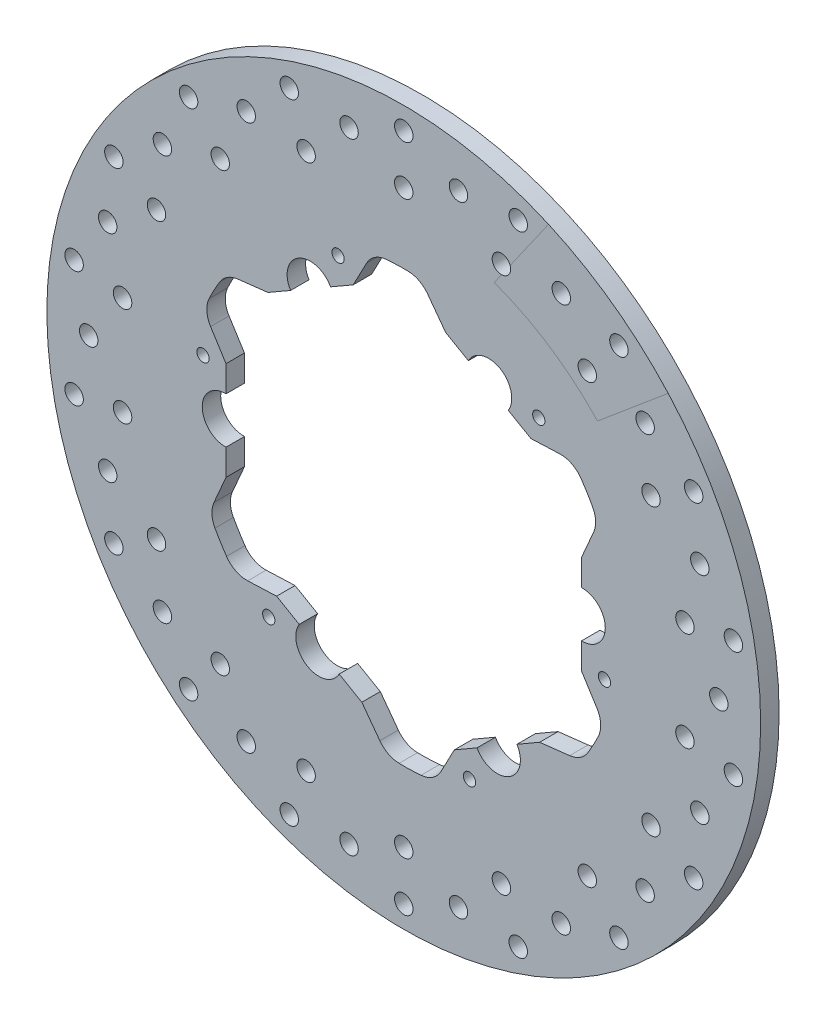
SolidWorks part; units mm, degrees
material "Gray Cast Iron"
ref_plane "Front Plane" through (0, 0, 0) normal (0, 0, 1) x (1, 0, 0)
ref_plane "Top Plane" through (0, 0, 0) normal (0, 1, 0) x (1, 0, 0)
ref_plane "Right Plane" through (0, 0, 0) normal (1, 0, 0) x (0, 0, -1)
sketch "Sketch1" plane through (0, 0, 0) normal (0, 0, 1) x (1, 0, 0)
  line L0 (-55.5625, 0) -> (-55.5625, -25.0191) construction
  line L1 (-45.8597, 11.4094) -> (-45.8597, 4.6599)
  line L2 (-45.8597, 11.4094) -> (-51.6236, 20.5474)
  line L3 (-45.8597, -13.9906) -> (-50.1583, -23.9026)
  line L4 (-45.8597, -7.2411) -> (-45.8597, -13.9906)
  line L5 (-13.049, 45.4204) -> (-8.0172, 54.981)
  line L6 (-13.049, 45.4204) -> (-18.8943, 42.0456)
  line L7 (-29.2008, 36.0951) -> (-35.0461, 32.7204)
  line L8 (-35.0461, 32.7204) -> (-45.7794, 31.4871)
  line L9 (32.8107, 34.011) -> (43.6064, 34.4336)
  line L10 (32.8107, 34.011) -> (26.9654, 37.3857)
  line L11 (16.6589, 43.3362) -> (10.8136, 46.711)
  line L12 (10.8136, 46.711) -> (4.3789, 55.3897)
  line L13 (45.8597, -11.4094) -> (51.6236, -20.5474)
  line L14 (45.8597, -11.4094) -> (45.8597, -4.6599)
  line L15 (45.8597, 7.2411) -> (45.8597, 13.9906)
  line L16 (45.8597, 13.9906) -> (50.1583, 23.9026)
  line L17 (13.049, -45.4204) -> (8.0172, -54.981)
  line L18 (13.049, -45.4204) -> (18.8943, -42.0456)
  line L19 (29.2008, -36.0951) -> (35.0461, -32.7204)
  line L20 (35.0461, -32.7204) -> (45.7794, -31.4871)
  line L21 (-32.8107, -34.011) -> (-43.6064, -34.4336)
  line L22 (-32.8107, -34.011) -> (-26.9654, -37.3857)
  line L23 (-16.6589, -43.3362) -> (-10.8136, -46.711)
  line L24 (-10.8136, -46.711) -> (-4.3789, -55.3897)
  circle A0 centre (0, 0) radius 92.075
  arc A1 (-45.7794, 31.4871) -> (-51.6236, 20.5474) centre (0, 0) ccw
  arc A3 (-45.8597, 4.6599) -> (-45.8597, -7.2411) centre (-46.0375, -1.2906) ccw
  arc A4 (-18.8943, 42.0456) -> (-29.2008, 36.0951) centre (-24.1364, 39.2243) ccw
  arc A5 (26.9654, 37.3857) -> (16.6589, 43.3362) centre (21.9011, 40.5149) ccw
  arc A6 (45.8597, -4.6599) -> (45.8597, 7.2411) centre (46.0375, 1.2906) ccw
  arc A7 (18.8943, -42.0456) -> (29.2008, -36.0951) centre (24.1364, -39.2243) ccw
  arc A8 (-26.9654, -37.3857) -> (-16.6589, -43.3362) centre (-21.9011, -40.5149) ccw
  arc A9 (4.3789, 55.3897) -> (-8.0172, 54.981) centre (0, 0) ccw
  arc A10 (50.1583, 23.9026) -> (43.6064, 34.4336) centre (0, 0) ccw
  arc A11 (45.7794, -31.4871) -> (51.6236, -20.5474) centre (0, 0) ccw
  arc A12 (-4.3789, -55.3897) -> (8.0172, -54.981) centre (0, 0) ccw
  arc A13 (-55.5625, 0) -> (-43.6064, -34.4336) centre (0, 0) ccw
  point P50 (0, 0)
  dimension "D1" = 184.15
  dimension "D2" = 111.125
  dimension "D3" = 11.9062
  dimension "D4" = 9.525
  dimension "D5" = 0.1778
  dimension "D6" = 25.4
  dimension "D7" = 44.45
  dimension "D9" = 47.2577
  dimension "D8" = 6
extrude "Boss-Extrude1" add sketch "Sketch1" along normal blind 4.7625 contours A0 A1 region at (-89.4707, 0, 0)
fillet "Fillet1" radius 6.35 12 edges at (8.0172, -54.981, 2.3813) (45.7794, -31.4871, 2.3813) (-4.3789, -55.3897, 2.3813) (-43.6064, -34.4336, 2.3813) (51.6236, -20.5474, 2.3813) (50.1583, 23.9026, 2.3813) (43.6064, 34.4336, 2.3813) (4.3789, 55.3897, 2.3813) (-50.1583, -23.9026, 2.3813) (-51.6236, 20.5474, 2.3813) (-8.0172, 54.981, 2.3813) (-45.7794, 31.4871, 2.3813)
sketch "Sketch4" plane through (0, 0, 4.7625) normal (0, 0, 1) x (1, 0, 0)
  circle A0 centre (-16.953, 50.0113) radius 1.5875
  arc A1 (-18.8943, 42.0456) -> (-29.2008, 36.0951) centre (-24.1364, 39.2243) ccw construction
  circle A3 centre (34.8346, 39.6874) radius 1.5875
  circle A4 centre (51.7876, -10.3239) radius 1.5875
  circle A5 centre (16.953, -50.0113) radius 1.5875
  circle A6 centre (-34.8346, -39.6874) radius 1.5875
  circle A7 centre (-51.7876, 10.3239) radius 1.5875
  point P6 (-27.113, 44.3799)
  point P23 (0, 0)
  dimension "D1" = 52.8066
  dimension "D2" = 3.175
  dimension "D3" = 10.16
  dimension "D4" = 6
extrude "Cut-Extrude1" cut sketch "Sketch4" against normal through all
sketch "Sketch5" plane through (0, 0, 4.7625) normal (0, 0, 1) x (1, 0, 0)
  line L0 (0, 120.6115) -> (0, 84.6416) construction
  line L1 (-74.0774, 0) -> (83.9652, 0) construction
  line L2 (0, 0) -> (20.7529, 117.6956) construction
  circle A0 centre (0, 0) radius 68.58 construction
  circle A4 centre (0, 86.36) radius 2.3812
  circle A5 centre (0, 73.66) radius 2.3812
  circle A6 centre (14.1141, 80.0452) radius 2.3812
  dimension "D1" = 137.16
  dimension "D2" = 4.7625
  dimension "D3" = 12.7
  dimension "D4" = 86.36
  dimension "D5" = 10
  dimension "D6" = 81.28
extrude "Cut-Extrude2" cut sketch "Sketch5" against normal through all
sketch "Sketch6" plane through (0, 0, 4.7625) normal (0, 0, 1) x (1, 0, 0)
  line L0 (0, 0) -> (0, 110.5188) construction
  line L1 (0, 0) -> (38.9978, 107.1456) construction
  line L4 (23.3472, 64.1458) -> (37.3582, 84.1556)
  line L5 (49.9701, 46.5054) -> (68.2294, 61.8268)
  arc A2 (68.2294, 61.8268) -> (37.3582, 84.1556) centre (0, 0) ccw
  arc A3 (49.9701, 46.5054) -> (23.3472, 64.1458) centre (0, 0) ccw
  dimension "D2" = 15
  dimension "D3" = 184.15
  dimension "D6" = 136.525
  dimension "D1" = 20
  dimension "D4" = 15
  dimension "D5" = 38.1
split line "Split Line1"
pattern_circular "FrontPaternCopy" count 18 over 360 about axis through (0, 0, 4.7625) along (0, 0, 1) of "Cut-Extrude2"
sketch "Sketch7" plane through (0, 0, 4.7625) normal (0, 0, 1) x (1, 0, 0)
  line L0 (0, 0) -> (-24.1364, 39.2243) construction
move or copy body "Body-Move/Copy1" [suppressed] parameters "D1"=0, "D2"=0, "D3"=0
equation "\"holenumber\"=18"
equation "\"D1@FrontPaternCopy\"=\"holenumber\""
